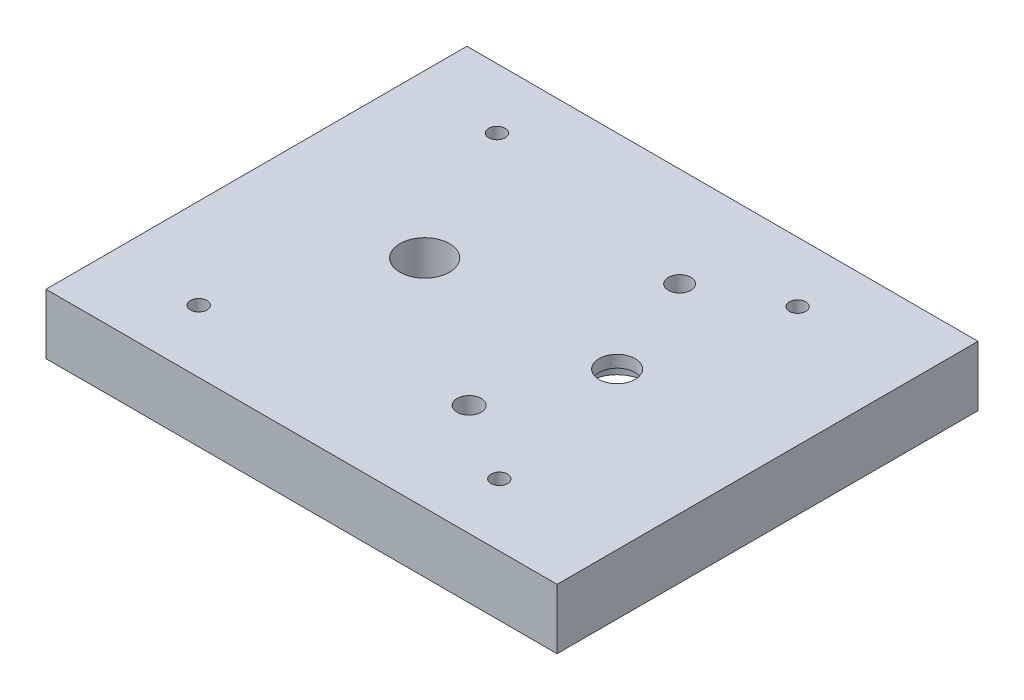
SolidWorks part; units mm, degrees
ref_plane "Front Plane" through (0, 0, 0) normal (0, 0, 1) x (1, 0, 0)
ref_plane "Top Plane" through (0, 0, 0) normal (0, 1, 0) x (1, 0, 0)
ref_plane "Right Plane" through (0, 0, 0) normal (1, 0, 0) x (0, 0, -1)
sketch "Sketch1" plane through (0, 0, 0) normal (0, 1, 0) x (1, 0, 0)
  line L0 (0, 8.2993) -> (0, -7.906) construction
  line L1 (-42.5, 35) -> (42.5, 35)
  line L2 (-42.5, 35) -> (-42.5, -35)
  line L3 (-42.5, -35) -> (42.5, -35)
  line L4 (42.5, 35) -> (42.5, -35)
  line L5 (-42.5, 35) -> (42.5, -35) construction
  line L6 (-42.5, -35) -> (42.5, 35) construction
  line L7 (-12.4915, 0.1967) -> (14.4413, 0.1967) construction
  line L8 (9.5, 1) -> (10.7497, 1) construction
  line L9 (37.5085, 0.1967) -> (64.4413, 0.1967) construction
  line L11 (15.0001, 2.9838) -> (15.0001, -1.0162)
  line L13 (17.9999, 3.0162) -> (17.9999, -0.9838)
  line L14 (15.0001, 2.9838) -> (17.9999, -0.9838) construction
  line L15 (15.0001, -1.0162) -> (17.9999, 3.0162) construction
  line L16 (12.9072, 18.471) -> (12.9072, 14.5791)
  line L17 (5.9072, 18.471) -> (5.9072, 14.5311)
  line L18 (12.9014, -16.529) -> (12.9014, -12.5805)
  line L19 (5.9014, -16.529) -> (5.9014, -12.5296)
  line L20 (-7.5, -6) -> (-7.5, 8)
  line L21 (-7.5, -6) -> (-2.6244, -6)
  line L22 (-7.5, 8) -> (-2.6244, 8)
  line L23 (-7.5, -3.7083) -> (-10.5, -3.7083)
  line L24 (-9.7318, -2.1549) -> (-9.7318, 4.1549)
  line L25 (-9.7318, 4.1549) -> (-7.5, 4.1549)
  line L26 (-15.52, 1) -> (-4.4975, 1) construction
  line L28 (-7.5, -4.399) -> (-7.5, 6.399)
  line L29 (-7.5, 6.399) -> (-7.7702, 6.399)
  line L31 (-7.5, -4.399) -> (-9.7318, 6.399) construction
  line L32 (-7.5, 6.399) -> (-9.7318, -4.399) construction
  line L33 (-9.7318, -2.1549) -> (-7.5, -2.1549)
  circle A0 centre (-27.5, 25) radius 1.375
  circle A1 centre (22.5, 25) radius 1.375
  circle A2 centre (22.5, -24.6067) radius 1.375
  circle A3 centre (-27.5, -24.6067) radius 1.375
  circle A4 centre (16.5, 1) radius 10
  circle A5 centre (-15.52, 1) radius 20
  arc A6 (15.0001, 2.9838) -> (17.9999, 3.0162) centre (16.5217, 1.0001) cw
  arc A7 (15.0001, -1.0162) -> (17.9999, -0.9838) centre (16.4783, 0.9999) ccw
  circle A8 centre (16.4783, 0.9999) radius 4.5
  circle A12 centre (-15.52, 1) radius 4.125
  circle A13 centre (16.4783, 0.9999) radius 3
  arc A14 (5.9072, 14.5311) -> (-2.6244, 8) centre (9.5, 1) ccw
  circle A17 centre (85.0307, -10.8481) radius 14
  circle A18 centre (86.1334, -28.3481) radius 2
  circle A19 centre (86.1334, 6.6519) radius 2
  arc A20 (5.9072, 14.5311) -> (-2.6244, 8) centre (9.5, 1) ccw
  circle A21 centre (9.4072, 18.471) radius 1.875
  circle A22 centre (9.4014, -16.529) radius 2
  arc A23 (12.9072, 18.471) -> (5.9072, 18.471) centre (9.4072, 18.471) ccw
  arc A24 (5.9014, -16.529) -> (12.9014, -16.529) centre (9.4014, -16.529) ccw
  arc A26 (12.9014, -12.5805) -> (12.9072, 14.5791) centre (9.5, 1) ccw
  arc A27 (12.9014, -12.5805) -> (12.9072, 14.5791) centre (9.5, 1) ccw
  arc A28 (-2.6244, -6) -> (5.9014, -12.5296) centre (9.5, 1) ccw
  arc A29 (-2.6244, -6) -> (5.9014, -12.5296) centre (9.5, 1) ccw
  point P0 (0, 0)
  point P61 (-8.6159, 1)
  point P71 (-9.7318, 1)
  dimension "D3" = 15
  dimension "D6" = 2.75
  dimension "D7" = 26
  dimension "D10" = 32.02
  dimension "D11" = 9
  dimension "D12" = 7
  dimension "D13" = 3.75
  dimension "D14" = 17
  dimension "D15" = 1.1027
  dimension "D17" = 1.1027
  dimension "D20" = 8.25
  dimension "D21" = 6
  dimension "D16" = 14
  dimension "D1" = 85
  dimension "D2" = 70
  dimension "D4" = 10
  dimension "D8" = 4
  dimension "D9" = 3
  dimension "D18" = 36
  dimension "D19" = 4
  dimension "D22" = 28.9915
  dimension "D23" = 7
  dimension "D24" = 3.9049
  dimension "D26" = 3.9049
  dimension "D27" = 3.9049
  dimension "D28" = 2.2917
  dimension "D29" = 0
  dimension "D30" = 10.798
  dimension "D5" = 2
extrude "Boss-Extrude4" add sketch "Sketch1" along normal blind 10 contours L4 L1 L2 L3 A14 A4 A5 A2 A1 A0 A3 | A14 A5 | A14 A4 | A5 A14 A4 | A5 A14 | A4 A14 A8 | A8 A13 | A4 A14 A5 | L16 A23 L17 A14 A20 A21 | L19 A24 L18 A14 A22 region at (0, 0, -33.8989) region at (12.4471, 0, -16.5251) region at (23.2375, 0, -1) region at (23.9705, 0, -1) region at (-1.3948, 0, -10.6321) region at (-1.393, 0, -1) region at (12.1056, 0, -0.9999)
sketch "Sketch2" plane through (0, 10, 0) normal (0, 1, 0) x (1, 0, 0)
  circle A3 centre (-15.52, 1) radius 9.125
  circle A4 centre (-15.52, 1) radius 9.125
  dimension "D1" = 5
extrude "Cut-Extrude2" cut sketch "Sketch1<7>" along normal blind 6 contours A8
sketch "Sketch1<7>" plane through (0, 0, 0) normal (0, 1, 0) x (1, 0, 0) same geometry as "Sketch1"
extrude "Cut-Extrude6" cut sketch "Sketch1<9>" along normal blind 6 contours L18 A26 A4 L16 A23 L17 A14 A5 L19 A24 A21 A22 | A5 A14 | A4 A26 A8 | L24 L33 L28 L25 region at (12.4471, 0, -16.5251) region at (23.2375, 0, -1) region at (-1.393, 0, -1) region at (-8.6159, 0, -1)
sketch "Sketch1<9>" plane through (0, 0, 0) normal (0, 1, 0) x (1, 0, 0) same geometry as "Sketch1"
extrude "Cut-Extrude10" cut sketch "Sketch1<11>" along normal blind 8 contours A8 A13 region at (12.1056, 0, -0.9999)
sketch "Sketch1<11>" plane through (0, 0, 0) normal (0, 1, 0) x (1, 0, 0) same geometry as "Sketch1"
sketch "Sketch5" plane through (0, 10, 0) normal (0, 1, 0) x (1, 0, 0)
  line L1 (-9.7318, -2.1549) -> (-7.5, -2.1549)
  line L2 (-9.7318, -2.1549) -> (-9.7318, 4.1549)
  line L3 (-9.7318, 4.1549) -> (-7.5, 4.1549)
  line L4 (-7.5, -2.1549) -> (-7.5, 4.1549)
extrude "Boss-Extrude5" add sketch "Sketch5" against normal blind 4
